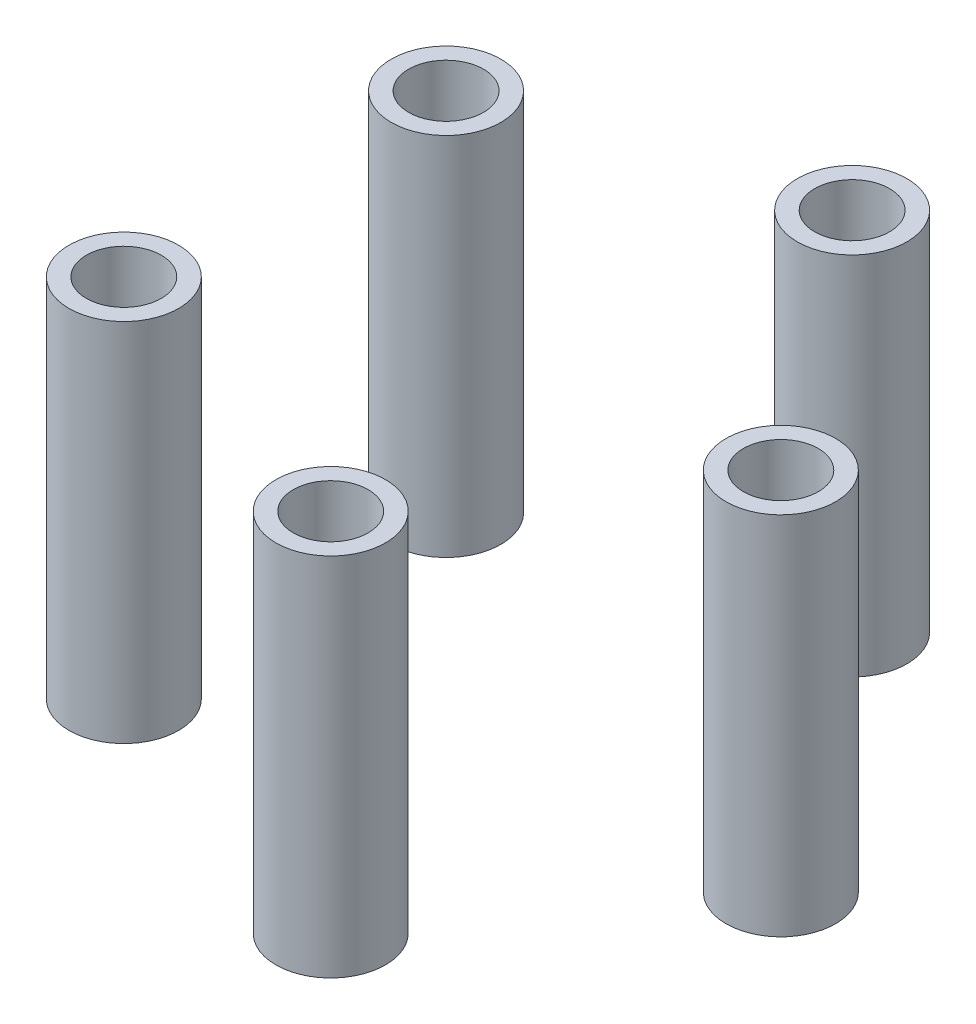
SolidWorks part; units mm, degrees
ref_plane "Front Plane" through (0, 0, 0) normal (0, 0, 1) x (1, 0, 0)
ref_plane "Top Plane" through (0, 0, 0) normal (0, 1, 0) x (1, 0, 0)
ref_plane "Right Plane" through (0, 0, 0) normal (1, 0, 0) x (0, 0, -1)
sketch "Sketch2" plane through (0, 0, 0) normal (0, 1, 0) x (1, 0, 0)
  line L0 (-16.0353, 8.8168) -> (-9.8353, 8.8209) construction
  line L1 (0.7353, 14.2658) -> (6.9353, 14.27) construction
  line L2 (11.1, 0) -> (17.3, 0.0042) construction
  line L3 (0.7353, -14.2658) -> (6.9353, -14.2617) construction
  line L4 (-16.0353, -8.8168) -> (-9.8353, -8.8126) construction
  circle A0 centre (-12.1353, 8.8168) radius 3.9 construction
  circle A1 centre (-13.7353, 8.8209) radius 3.9 construction
  circle A2 centre (4.6353, 14.2658) radius 3.9 construction
  circle A3 centre (3.0353, 14.27) radius 3.9 construction
  circle A4 centre (15, 0) radius 3.9 construction
  circle A5 centre (13.4, 0.0042) radius 3.9 construction
  circle A6 centre (4.6353, -14.2658) radius 3.9 construction
  circle A7 centre (3.0353, -14.2617) radius 3.9 construction
  circle A8 centre (-12.1353, -8.8168) radius 3.9 construction
  circle A9 centre (-13.7353, -8.8126) radius 3.9 construction
  circle A10 centre (14.2, 0.0021) radius 3
  circle A11 centre (14.2, 0.0021) radius 2.05
  circle A12 centre (3.8353, 14.2679) radius 3
  circle A13 centre (3.8353, 14.2679) radius 2.05
  circle A14 centre (-12.9353, 8.8189) radius 3
  circle A15 centre (-12.9353, 8.8189) radius 2.05
  circle A16 centre (-12.9353, -8.8147) radius 3
  circle A17 centre (-12.9353, -8.8147) radius 2.05
  circle A18 centre (3.8353, -14.2638) radius 3
  circle A19 centre (3.8353, -14.2638) radius 2.05
extrude "Boss-Extrude1" add sketch "Sketch2" along normal blind 10 and the other way blind 10
